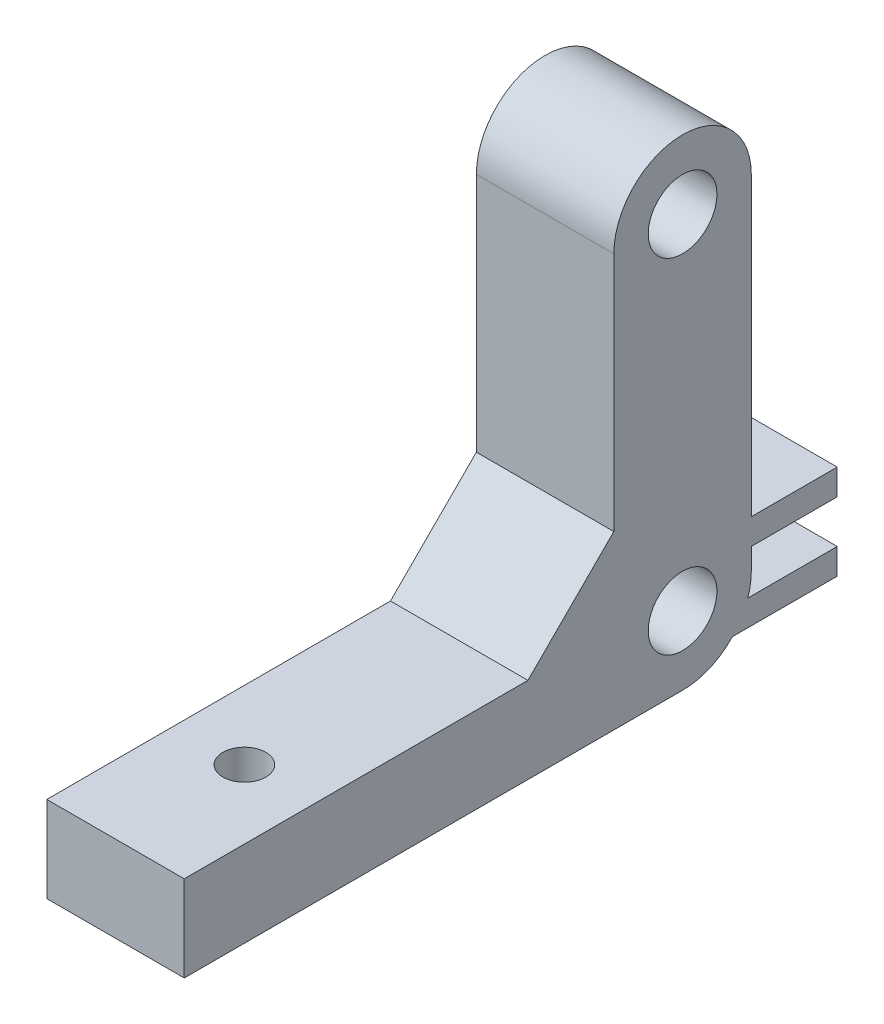
SolidWorks part; units mm, degrees
material "ABS"
ref_plane "Front Plane" through (0, 0, 0) normal (0, 0, 1) x (1, 0, 0)
ref_plane "Top Plane" through (0, 0, 0) normal (0, 1, 0) x (1, 0, 0)
ref_plane "Right Plane" through (0, 0, 0) normal (1, 0, 0) x (0, 0, -1)
sketch "Sketch1" plane through (0, 0, 0) normal (1, 0, 0) x (0, 0, -1)
  line L0 (-10.3091, -58.7899) -> (-58.9824, -58.7899)
  line L1 (7.0176, -45.2899) -> (17.0176, -45.2899)
  line L2 (-8.9824, -10.7899) -> (-8.9824, -38.7899)
  line L3 (-10.3091, -58.7899) -> (-0.9824, -58.7899)
  line L4 (7.0176, -10.7899) -> (7.0176, -45.2899)
  line L5 (-58.9824, -58.7899) -> (-58.9824, -48.7899)
  line L6 (-58.9824, -48.7899) -> (-18.9824, -48.7899)
  line L7 (-8.9824, -38.7899) -> (-18.9824, -48.7899)
  line L8 (17.0176, -45.2899) -> (17.0176, -48.2899)
  line L9 (17.0176, -48.2899) -> (7.0176, -48.2899)
  line L10 (4.8271, -56.2899) -> (17.0176, -56.2899)
  line L11 (17.0176, -56.2899) -> (17.0176, -53.2899)
  line L12 (17.0176, -53.2899) -> (6.617, -53.2899)
  line L13 (7.0176, -48.2899) -> (7.0176, -50.7899)
  circle A0 centre (-0.9824, -10.7899) radius 4
  circle A1 centre (-0.9824, -50.7899) radius 4
  arc A2 (-8.9824, -10.7899) -> (7.0176, -10.7899) centre (-0.9824, -10.7899) cw
  arc A3 (-0.9824, -58.7899) -> (4.8271, -56.2899) centre (-0.9824, -50.7899) ccw
  arc A4 (6.617, -53.2899) -> (7.0176, -50.7899) centre (-0.9824, -50.7899) ccw
  point P8 (-8.9824, -48.7899)
  dimension "D1" = 8
  dimension "D2" = 8
  dimension "D4" = 8
  dimension "D11" = 8
  dimension "D3" = 40
  dimension "D5" = 8
  dimension "D6" = 8
  dimension "D7" = 8
  dimension "D8" = 8
  dimension "D9" = 50
  dimension "D10" = 10
  dimension "D12" = 3
  dimension "D14" = 3
  dimension "D15" = 5
  dimension "D16" = 2.5
  dimension "D17" = 10
extrude "Boss-Extrude1" add sketch "Sketch1" against normal blind 16
sketch "Sketch2" plane through (0, -48.7899, 0) normal (0, 1, 0) x (1, 0, 0)
  line L0 (-16, -58.9824) -> (0, -58.9824) construction
  line L1 (0, -18.9824) -> (0, -58.9824) construction
  circle A0 centre (-8, -43.9824) radius 2.5
  dimension "D1" = 5
  dimension "D2" = 15
  dimension "D3" = 8
extrude "Cut-Extrude1" cut sketch "Sketch2" against normal through all
ref_point "Point1"
sketch "Sketch3" plane through (0, -45.2899, 0) normal (0, 1, 0) x (1, 0, 0)
  line L0 (-16, 17.0176) -> (0, 17.0176) construction
  line L1 (0, 17.0176) -> (0, 7.0176) construction
  circle A0 centre (-8, 12.0176) radius 2
  dimension "D1" = 4
  dimension "D2" = 5
  dimension "D3" = 8
extrude "Cut-Extrude2" cut sketch "Sketch3" against normal through all
equation "\"rod_diameter\"= 8"
equation "\"D1@Sketch1\" = \"rod_diameter\""
equation "\"D2@Sketch1\"=\"rod_diameter\""
equation "\"D5@Sketch1\"  = \"rod_radius\" + \"rod_hole_thickness\""
equation "\"D6@Sketch1\"  = \"rod_radius\" + \"rod_hole_thickness\""
equation "\"D7@Sketch1\"  = \"rod_radius\" + \"rod_hole_thickness\""
equation "\"rod_hole_thickness\"= 4"
equation "\"D8@Sketch1\"  = \"rod_radius\" + \"rod_hole_thickness\""
equation "\"D4@Sketch1\"  = \"rod_radius\" + \"rod_hole_thickness\""
equation "\"D11@Sketch1\" = \"rod_radius\" + \"rod_hole_thickness\""
equation "\"rod_radius\"= \"rod_diameter\" / 2"
equation "\"D1@Boss-Extrude1\"= \"rod_diameter\" + \"rod_hole_thickness\" * 2"
equation "\"D3@Sketch2\"=\"rod_radius\"+\"rod_hole_thickness\""
equation "\"platter_diameter\"= 320"
equation "\"platter_radius\"= \"platter_diameter\" / 2"
equation "\"extruder_mount_hole_spacing\"= 75"
equation "\"arm_rod_spacing\"= 40"
equation "\"D3@Sketch1\"=\"arm_rod_spacing\""
equation "\"D2@Sketch3\" = \"D17@Sketch1\" / 2"
equation "\"D3@Sketch3\"= \"D1@Boss-Extrude1\" / 2"
equation "\"top_frame_spacing\"= 90"
equation "\"motor_level_rod_spacing\"= 15"
equation "\"linear_bearing_diameter\"= 15"
equation "\"z_rod_spacing\"= 75"
equation "\"z_drive_rod_offset\"= 12"
equation "\"platter_rod_spacing\"= 50"
equation "\"rod_nut_thickness\"= 6.5"
equation "\"rod_nut_inscribed_diameter\"= 13"
equation "\"z_height\"= 400"
equation "\"gear_pitch\"=2"
equation "\"r_gear_teeth\"= 450"
equation "\"theta_gear_teeth\"= 385"
equation "\"sheet_thickness\"=5.333"
equation "\"sheet_tab_hole_thickness\"= \"sheet_thickness\""
equation "\"sheet_tab_width\"= \"sheet_thickness\"*2"
equation "\"sheet_double_tab_width\"= 35"
equation "\"sheet_bolt_diameter\"= 3"
equation "\"sheet_bolt_length\"= 16"
equation "\"sheet_nut_diameter\"= 5.5"
equation "\"sheet_nut_thickness\"= 2.5"
equation "\"sheet_nut_depth\"= 10"
equation "\"bearing_outside_diameter\"= 22"
equation "\"bearing_thickness\"= 7"
equation "\"corner_part_thickness\"= \"sheet_thickness\" + \"bearing_thickness\""
equation "\"setscrew_nut_diameter\"= 6"
equation "\"setscrew_nut_thickness\"= 3"
equation "\"setscrew_bolt_diameter\"= 3"
equation "\"motor_shaft_diameter\"= 5.7"
equation "\"printed_hole_tolerance\"= 1"
equation "\"D1@Sketch2\"=4.00 +\"printed_hole_tolerance\""
equation "\"D1@Sketch3\"=\"sheet_bolt_diameter\"+\"printed_hole_tolerance\""
